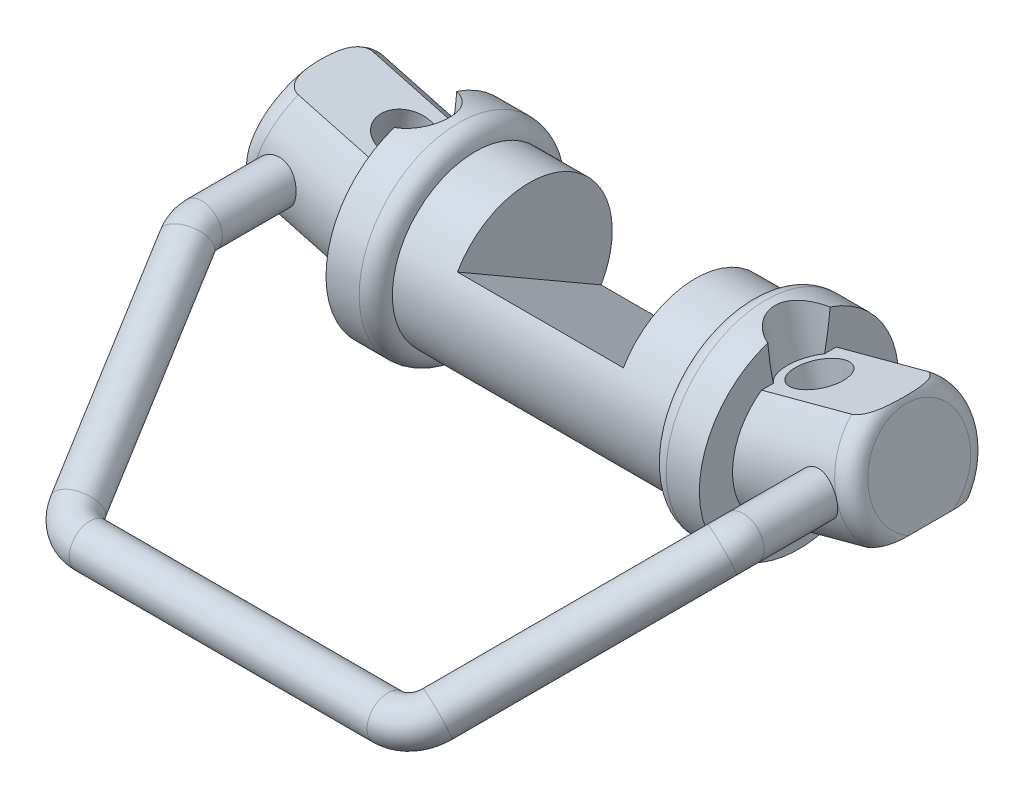
SolidWorks part; units mm, degrees
material "Alloy Steel"
ref_plane "Front Plane" through (0, 0, 0) normal (0, 0, 1) x (1, 0, 0)
ref_plane "Top Plane" through (0, 0, 0) normal (0, 1, 0) x (1, 0, 0)
ref_plane "Right Plane" through (0, 0, 0) normal (1, 0, 0) x (0, 0, -1)
sketch "Sketch3" plane through (0, 0, 0) normal (1, 0, 0) x (0, 0, -1)
  circle A0 centre (0, 0) radius 10
  dimension "D1" = 20
extrude "Boss-Extrude1" add sketch "Sketch3" along normal mid plane 45
sketch "Sketch5" plane through (0, 0, 0) normal (1, 0, 0) x (0, 0, -1)
  circle A0 centre (0, 0) radius 12
  dimension "D1" = 24
extrude "Boss-Extrude2" add sketch "Sketch5" along normal blind 6 from surface starting at face at (-22.5, 0, -10)
extrude "Boss-Extrude3" add sketch "Sketch5<2>" against normal blind 6 from surface starting at face at (22.5, 0, -10)
sketch "Sketch5<2>" plane through (0, 0, 0) normal (1, 0, 0) x (0, 0, -1) same geometry as "Sketch5"
fillet "Fillet1" radius 2 2 edges at (16.5, 0, -12) (-16.5, 0, -12)
ref_axis "Axis1" through (-22.5, 0, -13.2) along (0, 0, 1)
ref_plane "Plane1" through (-20.9928, 5.625, 0) normal (-0.9659, 0.2588, 0) x (0, 0, 1)
sketch "Sketch6" plane through (-20.9928, 5.625, 0) normal (-0.9659, 0.2588, 0) x (0, 0, 1)
  line L1 (-13.2, -5.8234) -> (13.2, -5.8234) construction
  line L2 (-5.9157, -11.2091) -> (5.9157, -11.2091)
  line L3 (-4.5, 0.7909) -> (4.5, 0.7909)
  circle A0 centre (0, -5.8234) radius 8
  dimension "D1" = 16
  dimension "D2" = 12
  dimension "D3" = 9
extrude "Boss-Extrude4" add sketch "Sketch6" along normal blind 15 and the other way blind 2 contours L2 A0 L3 region at (-22.3832, 0.436, 0)
fillet "Fillet2" radius 2 2 edges at (-36.7463, 4.7876, 7.9449) (-36.7463, 4.7876, -7.9449)
mirror "Mirror1" about plane through (0, 0, 0) normal (1, 0, 0) of "Fillet2", "Boss-Extrude4"
ref_axis "Axis2" through (-42.5403, 0, 0) along (1, 0, 0)
ref_plane "Plane2" through (0, 0, 0) normal (0, 0.5, 0.866) x (1, 0, 0)
sketch "Sketch7" plane through (0, 0, 0) normal (0, 0.5, 0.866) x (1, 0, 0)
  line L0 (16.5, 10) -> (-16.5, 10) construction
  line L1 (10, 0) -> (-10, 0)
  line L2 (0, 0) -> (0, 10)
  line L3 (10, 10) -> (-10, 10)
  line L4 (-10, 0) -> (-10, 10)
  line L5 (10, 0) -> (10, 10)
  dimension "D1" = 10
extrude "Cut-Extrude1" cut sketch "Sketch7" against normal up to next and the other way up to next contours L1 L4 L3 L5
sketch "Sketch8" plane through (0, 0, 0) normal (0, 0, 1) x (1, 0, 0)
  line L0 (0, 0) -> (0, 23.0961) construction
  line L1 (-20.4294, 7.7274) -> (-24.5706, -7.7274) construction
  line L2 (-20.4294, 7.7274) -> (-24.5706, -7.7274)
  line L3 (-22.5, 0) -> (-38.7613, 4.3572) construction
  line L4 (-33.3451, 9.7536) -> (-36.4509, -1.8375) construction
  circle A0 centre (-32.6422, 2.7176) radius 2.5
  circle A1 centre (32.6422, 2.7176) radius 2.5
  dimension "D1" = 5
sketch3d "3DSketch1"
  line L0 (-32.6422, 2.7176, 0) -> (-32.6422, 2.7176, 16.8473)
  line L1 (-32.2085, 2.2839, 18.9759) -> (-21.6555, -8.2691, 42.7202)
  line L2 (0, 0, 0) -> (0, 0, 45) construction
  line L3 (-32.6422, 2.7176, 18) -> (-32.6422, 2.7176, 45) construction
  line L4 (-32.6422, 2.7176, 45) -> (-20.6422, 2.7176, 45) construction
  line L5 (-20.6422, 2.7176, 45) -> (-20.6422, -9.2824, 45) construction
  line L6 (-17.9495, -9.2824, 45) -> (17.9495, -9.2824, 45)
  line L7 (0, 0, 45) -> (0, -18.5648, 45) construction
  line L8 (32.6422, 2.7176, 0) -> (32.6422, 2.7176, 16.8473)
  line L9 (32.2085, 2.2839, 18.9759) -> (21.6555, -8.2691, 42.7202)
  arc A0 (32.6422, 2.7176, 16.8473) -> (32.2085, 2.2839, 18.9759) centre (29.8138, -0.1108, 16.8473) ccw
  arc A1 (-32.6422, 2.7176, 16.8473) -> (-32.2085, 2.2839, 18.9759) centre (-29.8138, -0.1108, 16.8473) ccw
  arc A2 (21.6555, -8.2691, 42.7202) -> (17.9495, -9.2824, 45) centre (17.9495, -7.6578, 41.3448) ccw
  arc A3 (-21.6555, -8.2691, 42.7202) -> (-17.9495, -9.2824, 45) centre (-17.9495, -7.6578, 41.3448) ccw
  point P15 (0, -9.2824, 45)
  point P17 (32.6422, 2.7176, 18)
  point P18 (32.6422, -2.9393, 16.8473)
  point P21 (-32.6422, 2.7176, 18)
  point P23 (-26.9854, 2.7176, 16.8473)
  point P26 (20.6422, -9.2824, 45)
  point P27 (17.9495, -11.3131, 39.7202)
  point P30 (-20.6422, -9.2824, 45)
  point P32 (-17.9495, -4.0026, 42.9693)
  dimension "D5" = 4
  dimension "D1" = 18
  dimension "D2" = 27
  dimension "D3" = 12
  dimension "D4" = 12
sweep "Sweep1" add profiles "Sketch8" path "3DSketch1"
sketch "Sketch9" plane through (0.2047, 0.764, 0) normal (0.2588, 0.9659, 0) x (0.9659, -0.2588, 0)
  line L0 (-23.5056, 4.5) -> (-34.7333, 4.5) construction
  line L1 (-23.5056, -4.5) -> (-23.5056, 4.5) construction
  circle A0 centre (-26.0544, 0) radius 3
  circle A3 centre (-26.0544, 0) radius 4
  dimension "D1" = 6
  dimension "D2" = 8
  dimension "D3" = 4.5
  dimension "D4" = 2.5487
sketch "Sketch10" plane through (-0.2047, 0.764, 0) normal (-0.2588, 0.9659, 0) x (0.9659, 0.2588, 0)
  line L0 (23.5056, 4.5) -> (23.5056, -4.5) construction
  line L1 (23.5056, 4.5) -> (34.7333, 4.5) construction
  circle A0 centre (26.0544, 0) radius 3
  circle A3 centre (26.0544, 0) radius 4
  dimension "D1" = 6
  dimension "D2" = 8
  dimension "D3" = 2.5487
  dimension "D4" = 4.5
extrude "Cut-Extrude2" cut sketch "Sketch9" against normal up to next and the other way up to next contours A0
extrude "Cut-Extrude3" cut sketch "Sketch10" against normal up to next and the other way up to next contours A0
extrude "Cut-Extrude4" cut sketch "Sketch9<3>" along normal up to next
sketch "Sketch9<3>" plane through (0.2047, 0.764, 0) normal (0.2588, 0.9659, 0) x (0.9659, -0.2588, 0) same geometry as "Sketch9"
extrude "Cut-Extrude5" cut sketch "Sketch10<3>" along normal up to next
sketch "Sketch10<3>" plane through (-0.2047, 0.764, 0) normal (-0.2588, 0.9659, 0) x (0.9659, 0.2588, 0) same geometry as "Sketch10"
